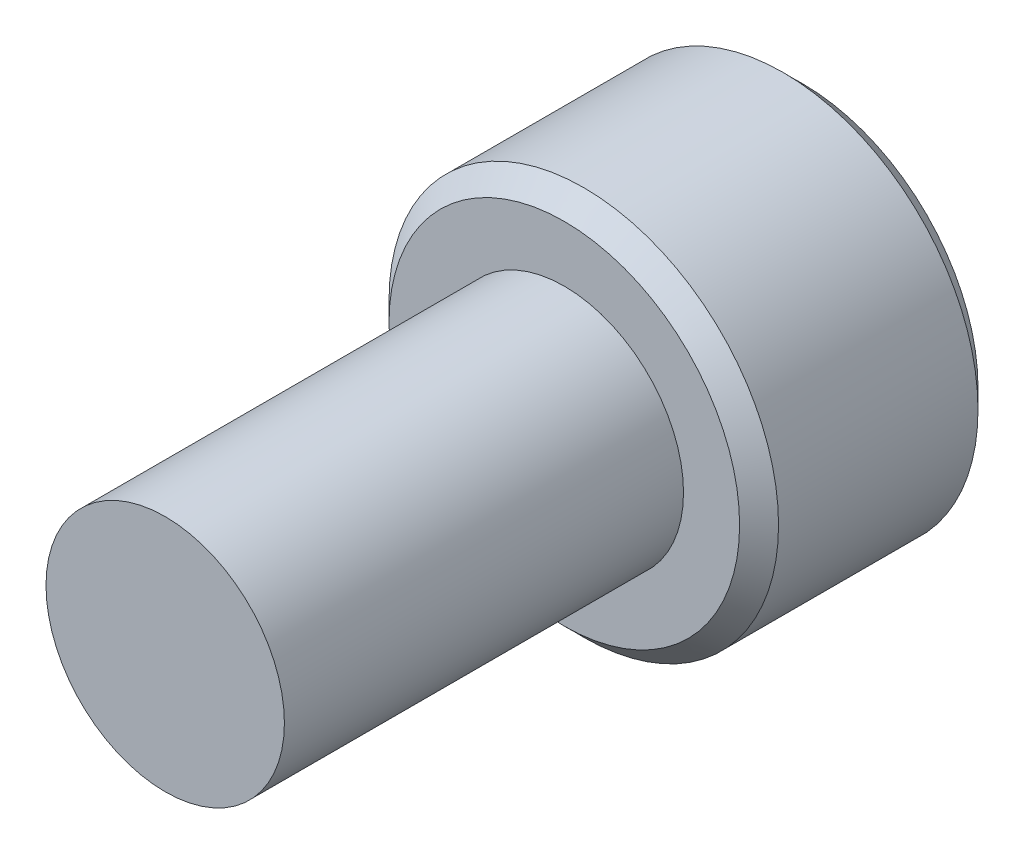
SolidWorks part; units mm, degrees
material "6061 Alloy"
ref_plane "Front Plane" through (0, 0, 0) normal (0, 0, 1) x (1, 0, 0)
ref_plane "Top Plane" through (0, 0, 0) normal (0, 1, 0) x (1, 0, 0)
ref_plane "Right Plane" through (0, 0, 0) normal (1, 0, 0) x (0, 0, -1)
sketch "Sketch1" plane through (0, 0, 0) normal (0, 0, 1) x (1, 0, 0)
  circle A0 centre (0, 0) radius 1.4224
  dimension "OD" = 2.8448
extrude "Extrude1" add sketch "Sketch1" against normal blind 4.7625
sketch "Sketch2" plane through (0, 0, 0) normal (0, 0, 1) x (1, 0, 0)
  circle A0 centre (0, 0) radius 1.4224 construction
  circle A1 centre (0, 0) radius 1.4224
curve "Helix/Spiral1" pitch 0.635 height 5.3975 turns 8.5 parameters "pitch"=0.635
sketch "Sketch3" plane through (0, 0, 0) normal (1, 0, 0) x (0, 0, -1)
  line L0 (-0.5556, 1.4224) -> (-0.3175, 1.01)
  line L1 (-0.3175, 1.01) -> (-0.2381, 1.01)
  line L2 (-0.2381, 1.01) -> (0, 1.4224)
  line L3 (-0.5556, 1.4224) -> (0, 1.4224)
  line L4 (-0.2778, 1.4224) -> (-0.2778, 1.01) construction
  line L5 (-0.4366, 1.2162) -> (-0.1191, 1.2162) construction
  line L6 (0, 1.4224) -> (0, -1.4224) construction
  dimension "D1" = 0.0794
  dimension "D2" = 0.3175
  dimension "D3" = 60
sketch "Sketch4" plane through (0, 0, 0) normal (1, 0, 0) x (0, 0, -1)
  line L0 (0.4666, 1.4224) -> (0, 0.756)
  line L1 (0, 0.756) -> (0, 1.4224)
  line L2 (0.4666, 1.4224) -> (0, 1.4224)
  line L3 (-0.5556, 1.4224) -> (0, 1.4224) construction
  line L4 (0, 0) -> (7.0209, 0) construction
  dimension "D1" = 55
  dimension "D2" = 0.254
sketch "Sketch6" plane through (0, 0, -4.7625) normal (0, 0, -1) x (-1, 0, 0)
  circle A0 centre (0, 0) radius 2.3241
  dimension "head dia" = 4.6482
extrude "Extrude2" add sketch "Sketch6" along normal blind 2.8448
sketch "Sketch7" plane through (0, 0, -7.6073) normal (0, 0, -1) x (-1, 0, 0)
  line L1 (0, 1.3748) -> (-1.1906, 0.6874)
  line L2 (-1.1906, 0.6874) -> (-1.1906, -0.6874)
  line L3 (-1.1906, -0.6874) -> (0, -1.3748)
  line L4 (0, -1.3748) -> (1.1906, -0.6874)
  line L5 (1.1906, -0.6874) -> (1.1906, 0.6874)
  line L6 (1.1906, 0.6874) -> (0, 1.3748)
  circle A0 centre (0, 0) radius 1.1906 construction
  dimension "hex dia" = 2.3813
extrude "Cut-Extrude1" cut sketch "Sketch7" against normal blind 1.7859
sketch "Sketch8" plane through (0, 0, -7.6073) normal (0, 0, -1) x (-1, 0, 0)
  circle A0 centre (0, 0) radius 1.3748
extrude "Cut-Extrude2" cut sketch "Sketch8" against normal through all draft 45
chamfer "Chamfer1" distance 0.2324 angle 45 2 edges at (-2.3241, 0, -7.6073) (-2.3241, 0, -4.7625)
sketch "Sketch10" plane through (0, 0, -4.7625) normal (0, 0, 1) x (1, 0, 0)
  circle A1 centre (0, 0) radius 1.4224
  circle A2 centre (0, 0) radius 1.4224
  dimension "D1" = 0
ref_plane "Plane1" through (0, 0, 0) normal (0, 0, 1) x (1, 0, 0)
extrude "partial thread" [suppressed] add sketch "Sketch10" along normal up to surface (12.7 mm away) separate body up to plane "Plane1"
chamfer "Chamfer2" [suppressed] distance 0.0569 angle 45
combine bodies "Combine1" [suppressed] operation type add bodies to combine 107 108
sketch "Sketch9" plane through (0, 0, 0) normal (1, 0, 0) x (0, 0, -1)
  line L0 (0, 1.4224) -> (0, -1.4224) construction
  line L1 (1.5875, 1.4224) -> (1.5875, -1.4224) construction
  dimension "D1" = 1.5875
equation "\"D3@Helix/Spiral1\" = \"screw length@Extrude1\"+\"pitch@Helix/Spiral1\""
equation "\"D1@Sketch3\" = \"pitch@Helix/Spiral1\"*.125"
equation "\"D2@Sketch3\" = \"pitch@Helix/Spiral1\"*.5"
equation "\"D1@Cut-Extrude1\" = \"hex dia@Sketch7\"*.75"
equation "\"D1@Chamfer1\" = \"head dia@Sketch6\"*.05"
equation "\"D1@Sketch9\" = \"pitch@Helix/Spiral1\"*2.5"
equation "\"D1@Chamfer2\"=\"OD@Sketch1\"*.02"
